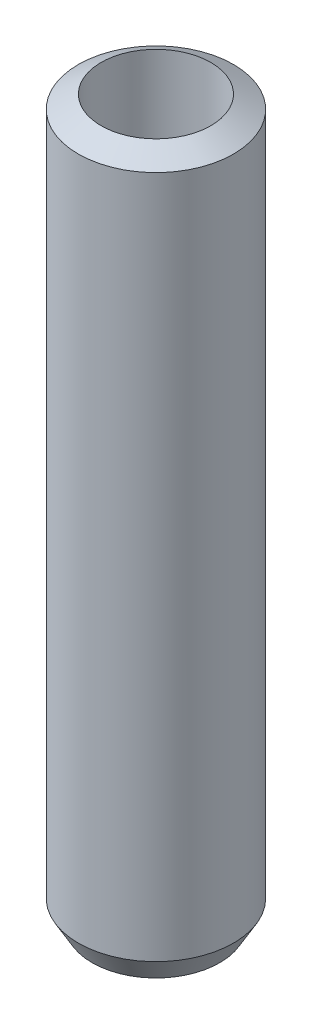
SolidWorks part; units mm, degrees
ref_plane "Front Plane" through (0, 0, 0) normal (0, 0, 1) x (1, 0, 0)
ref_plane "Top Plane" through (0, 0, 0) normal (0, 1, 0) x (1, 0, 0)
ref_plane "Right Plane" through (0, 0, 0) normal (1, 0, 0) x (0, 0, -1)
sketch "Sketch1" plane through (0, 0, 0) normal (0, 1, 0) x (1, 0, 0)
  circle A0 centre (0, 0) radius 20
  dimension "SHAFT_OD" = 40
extrude "Boss-Extrude1" add sketch "Sketch1" along normal blind 185.8189
sketch "Sketch2" plane through (0, 0, 0) normal (0, 1, 0) x (1, 0, 0)
  circle A0 centre (0, 0) radius 14.1352
  dimension "BORE_D" = 28.2704
extrude "Cut-Extrude1" cut sketch "Sketch2" along normal through all
chamfer "Chamfer1" distance 3.5631 angle 60 2 edges at (0, 185.8189, 20) (0, 0, 20) first distance on face at (0, 185.8189, 20) first distance on face at (0, 0, 14.1352)
